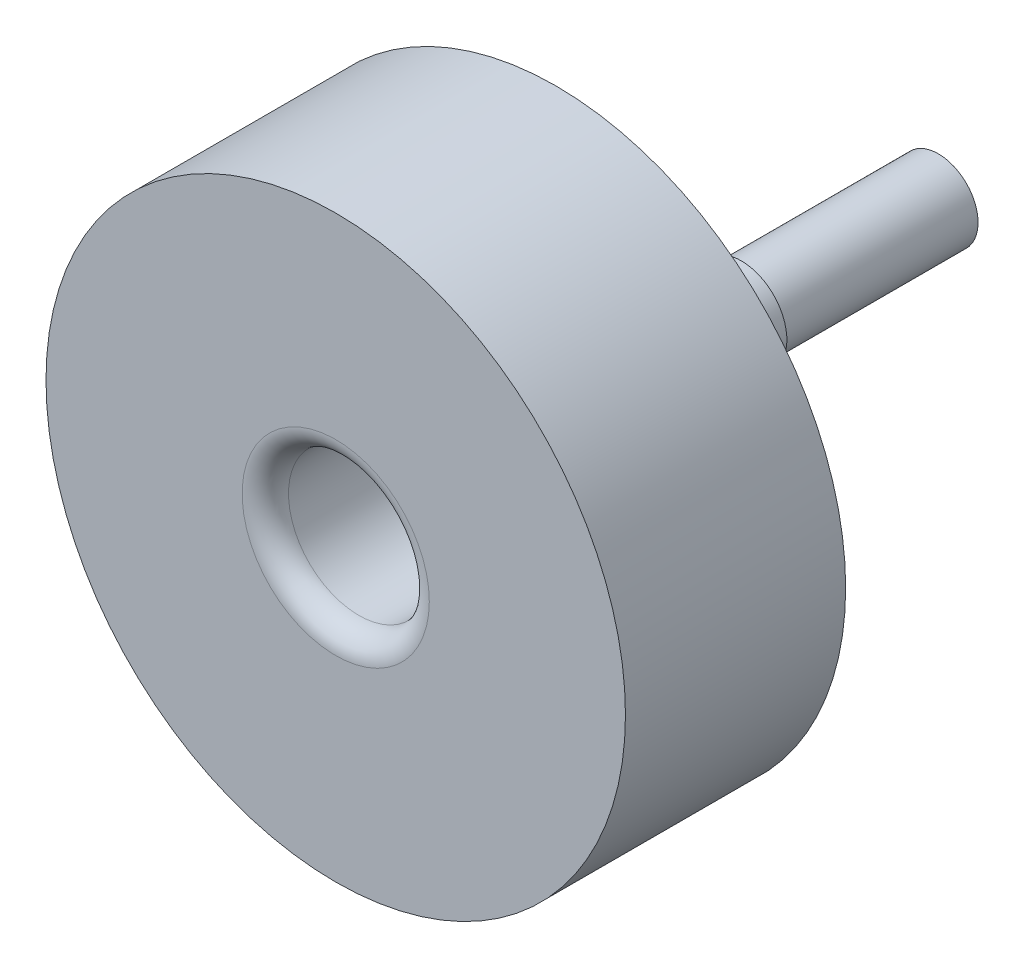
SolidWorks part; units mm, degrees
ref_plane "Ebene vorne" through (0, 0, 0) normal (0, 0, 1) x (1, 0, 0)
ref_plane "Ebene oben" through (0, 0, 0) normal (0, 1, 0) x (1, 0, 0)
ref_plane "Ebene rechts" through (0, 0, 0) normal (1, 0, 0) x (0, 0, -1)
sketch "Skizze1" plane through (0, 0, 0) normal (0, 0, 1) x (1, 0, 0)
  circle A0 centre (0, 0) radius 6
  dimension "D1" = 12
extrude "Aufsatz-Linear austragen1" add sketch "Skizze1" along normal blind 9
sketch "Skizze2" plane through (0, 0, 0) normal (0, 0, -1) x (-1, 0, 0)
  circle A0 centre (0, 0) radius 3.925
  dimension "D1" = 7.85
extrude "Aufsatz-Linear austragen2" add sketch "Skizze2" along normal blind 7
sketch "Skizze3" plane through (0, 0, 9) normal (0, 0, 1) x (1, 0, 0)
  circle A0 centre (0, 0) radius 25
  dimension "D1" = 50
extrude "Aufsatz-Linear austragen3" add sketch "Skizze3" along normal blind 19
sketch "Skizze4" plane through (0, 0, 28) normal (0, 0, 1) x (1, 0, 0)
  circle A0 centre (0, 0) radius 6.075
  dimension "D1" = 12.15
extrude "Schnitt-Linear austragen2" cut sketch "Skizze4" against normal blind 10
fillet "Verrundung1" radius 2 1 edges at (6.075, 0, 28)
sketch "Skizze5" plane through (0, 0, -7) normal (0, 0, -1) x (-1, 0, 0)
  circle A0 centre (0, 0) radius 3.425
  dimension "D1" = 6.85
extrude "Aufsatz-Linear austragen4" add sketch "Skizze5" along normal blind 17
